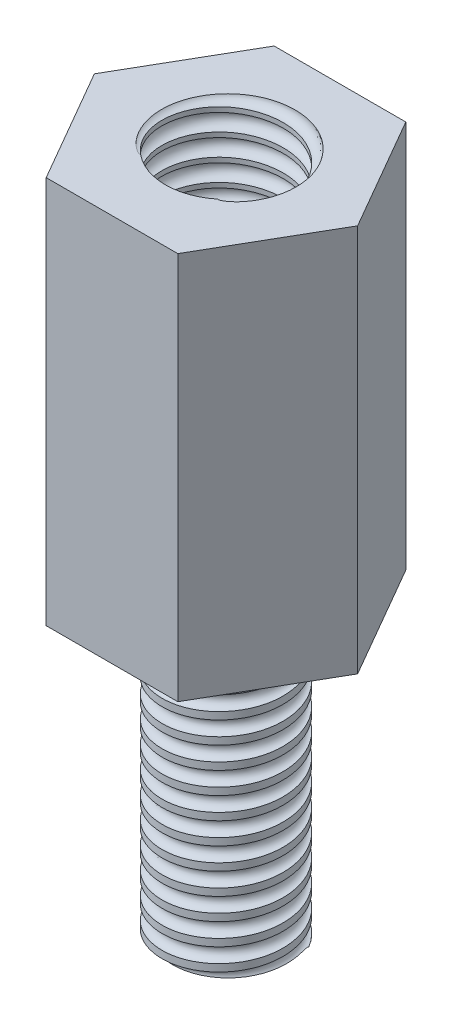
SolidWorks part; units mm, degrees
ref_plane "Front Plane" through (0, 0, 0) normal (0, 0, 1) x (1, 0, 0)
ref_plane "Top Plane" through (0, 0, 0) normal (0, 1, 0) x (1, 0, 0)
ref_plane "Right Plane" through (0, 0, 0) normal (1, 0, 0) x (0, 0, -1)
sketch "Sketch1" plane through (0, 0, 0) normal (0, 1, 0) x (1, 0, 0)
  line L1 (1.3568, -2.35) -> (2.7135, 0)
  line L2 (2.7135, 0) -> (1.3568, 2.35)
  line L3 (1.3568, 2.35) -> (-1.3568, 2.35)
  line L4 (-1.3568, 2.35) -> (-2.7135, 0)
  line L5 (-2.7135, 0) -> (-1.3568, -2.35)
  line L6 (-1.3568, -2.35) -> (1.3568, -2.35)
  circle A0 centre (0, 0) radius 2.35 construction
  point P1 (0, 2.35)
  dimension "D1" = 4.7
extrude "Boss-Extrude1" add sketch "Sketch1" along normal blind 8
sketch "Sketch2" plane through (0, 0, 0) normal (0, -1, 0) x (1, 0, 0)
  circle A0 centre (0, 0) radius 1.25
  dimension "D1" = 2.5
extrude "Boss-Extrude2" add sketch "Sketch2" along normal blind 6
sketch "Sketch4" plane through (0, -6, 0) normal (0, -1, 0) x (1, 0, 0)
  circle A0 centre (0, 0) radius 1.25 construction
  circle A1 centre (0, 0) radius 1.25
curve "Helix/Spiral1" pitch 0.45 height 5.9625 turns 13.25
sketch "Sketch5" plane through (0, 0, 0) normal (1, 0, 0) x (0, 0, -1)
  circle A0 centre (-1.25, -6) radius 0.15
  dimension "D1" = 0.3
sweep "Cut-Sweep3" cut profiles "Sketch5" path "Helix/Spiral1"
sketch "Sketch9" plane through (0, 8, 0) normal (0, 1, 0) x (1, 0, 0)
  circle A0 centre (0, 0) radius 1.25
  dimension "D1" = 2.5
extrude "Cut-Extrude1" cut sketch "Sketch9" against normal blind 6
sketch "Sketch10" plane through (0, 8, 0) normal (0, 1, 0) x (1, 0, 0)
  circle A0 centre (0, 0) radius 1.25 construction
  circle A1 centre (0, 0) radius 1.25
curve "Helix/Spiral2" pitch 0.45 height 5.9625 turns 13.25
sketch "Sketch11" plane through (0, 0, 0) normal (1, 0, 0) x (0, 0, -1)
  circle A0 centre (1.25, 8) radius 0.175
  dimension "D1" = 0.35
sweep "Cut-Sweep4" cut profiles "Sketch11" path "Helix/Spiral2"
